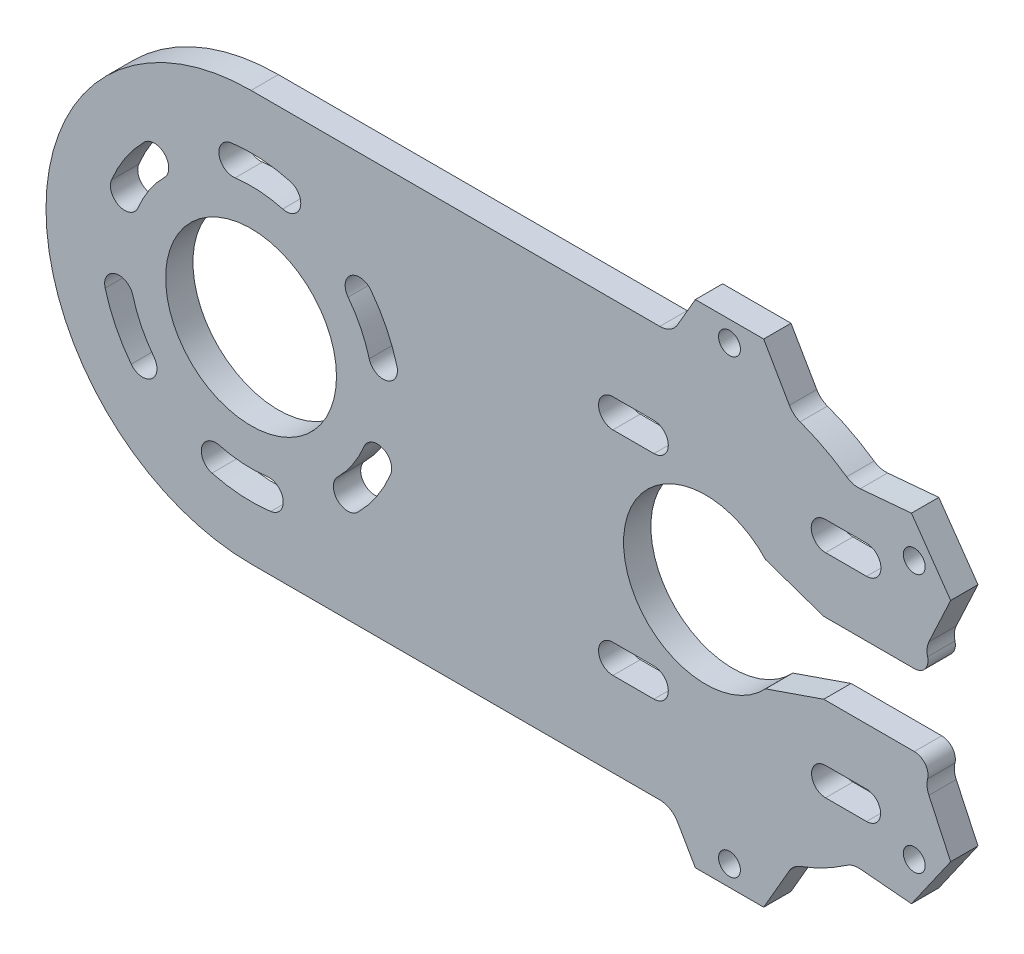
SolidWorks part; units mm, degrees
material "7075-T6 (SN)"
ref_plane "Ebene vorne" through (0, 0, 0) normal (0, 0, 1) x (1, 0, 0)
ref_plane "Ebene oben" through (0, 0, 0) normal (0, 1, 0) x (1, 0, 0)
ref_plane "Ebene rechts" through (0, 0, 0) normal (1, 0, 0) x (0, 0, -1)
sketch "Skizze1" plane through (0, 0, 0) normal (0, 0, 1) x (1, 0, 0)
  line L0 (60.6188, -25.1224) -> (53.122, -24.4665)
  line L1 (42.7599, -29.8607) -> (38.9972, -36.3779)
  line L2 (38.9972, -36.3779) -> (28.9972, -36.3779)
  line L3 (28.9972, -36.3779) -> (26.3991, -31.8779)
  line L4 (23.801, -30.3779) -> (-36.0028, -30.3779)
  line L5 (-36.0028, 29.6221) -> (23.801, 29.6221)
  line L6 (26.3991, 31.1221) -> (28.9972, 35.6221)
  line L7 (28.9972, 35.6221) -> (38.9972, 35.6221)
  line L8 (38.9972, 35.6221) -> (42.7599, 29.1049)
  line L9 (53.122, 23.7107) -> (60.6188, 24.3666)
  line L10 (60.6188, 24.3666) -> (66.3546, 16.1751)
  line L11 (66.3546, 16.1751) -> (63.1738, 9.3539)
  line L12 (61.0423, 4.8721) -> (47.7853, 4.8721)
  line L13 (47.7853, 4.8721) -> (39.265, 7.8151)
  line L14 (39.265, -8.5709) -> (47.7853, -5.6279)
  line L15 (47.7853, -5.6279) -> (61.0423, -5.6279)
  line L16 (63.1738, -10.1097) -> (66.3546, -16.9309)
  line L17 (66.3546, -16.9309) -> (60.6188, -25.1224)
  line L18 (54.0535, -13.8842) -> (48.0535, -13.8842)
  line L19 (48.0535, -17.9842) -> (54.0535, -17.9842)
  line L20 (22.9409, -13.8342) -> (16.9409, -13.8342)
  line L21 (16.9409, -18.0342) -> (22.9409, -18.0342)
  line L22 (54.0535, 17.2785) -> (48.0535, 17.2785)
  line L23 (48.0535, 13.0785) -> (54.0535, 13.0785)
  line L24 (22.9409, 17.2785) -> (16.9409, 17.2785)
  line L25 (16.9409, 13.0785) -> (22.9409, 13.0785)
  arc A0 (53.122, -24.4665) -> (51.1457, -24.9935) centre (52.8605, -27.4551) ccw
  arc A1 (44.3252, -28.544) -> (51.1457, -24.9935) centre (33.9972, -0.3779) ccw
  arc A2 (44.3252, -28.544) -> (42.7599, -29.8607) centre (45.358, -31.3607) ccw
  arc A3 (26.3991, -31.8779) -> (23.801, -30.3779) centre (23.801, -33.3779) ccw
  arc A4 (-36.0028, 29.6221) -> (-36.0028, -30.3779) centre (-36.0028, -0.3779) ccw
  arc A5 (23.801, 29.6221) -> (26.3991, 31.1221) centre (23.801, 32.6221) ccw
  arc A6 (42.7599, 29.1049) -> (44.3252, 27.7883) centre (45.358, 30.6049) ccw
  arc A7 (51.1457, 24.2378) -> (44.3252, 27.7883) centre (33.9972, -0.3779) ccw
  arc A8 (51.1457, 24.2378) -> (53.122, 23.7107) centre (52.8605, 26.6993) ccw
  arc A9 (63.1738, 9.3539) -> (62.9825, 7.3577) centre (65.8927, 8.086) ccw
  arc A10 (61.0423, 4.8721) -> (62.9825, 7.3577) centre (61.0423, 6.8721) ccw
  arc A11 (39.265, 7.8151) -> (39.265, -8.5709) centre (30.4972, -0.3779) ccw
  arc A12 (62.9825, -8.1135) -> (61.0423, -5.6279) centre (61.0423, -7.6279) ccw
  arc A13 (62.9825, -8.1135) -> (63.1738, -10.1097) centre (65.8927, -8.8418) ccw
  circle A14 centre (61.0292, -19.3059) radius 1.6
  circle A15 centre (33.9972, -33.3779) radius 1.6
  arc A16 (48.0535, -13.8842) -> (48.0535, -17.9842) centre (48.0535, -15.9342) ccw
  arc A17 (54.0535, -17.9842) -> (54.0535, -13.8842) centre (54.0535, -15.9342) ccw
  arc A18 (16.9409, -13.8342) -> (16.9409, -18.0342) centre (16.9409, -15.9342) ccw
  arc A19 (22.9409, -18.0342) -> (22.9409, -13.8342) centre (22.9409, -15.9342) ccw
  arc A20 (-40.6357, -17.668) -> (-33.6664, -18.1248) centre (-36.0028, -0.3779) ccw
  arc A21 (-40.6357, -17.668) -> (-41.7227, -21.7248) centre (-41.1792, -19.6964) ccw
  arc A22 (-41.7227, -21.7248) -> (-33.1182, -22.2888) centre (-36.0028, -0.3779) ccw
  arc A23 (-33.1182, -22.2888) -> (-33.6664, -18.1248) centre (-33.3923, -20.2068) ccw
  arc A24 (-20.3757, -16.0049) -> (-15.5851, -8.8352) centre (-36.0028, -0.3779) ccw
  arc A25 (-15.5851, -8.8352) -> (-19.4654, -7.2279) centre (-17.5252, -8.0316) ccw
  arc A26 (-23.3456, -13.0351) -> (-19.4654, -7.2279) centre (-36.0028, -0.3779) ccw
  arc A27 (-23.3456, -13.0351) -> (-20.3757, -16.0049) centre (-21.8607, -14.52) ccw
  arc A28 (-53.5359, -13.8315) -> (-50.2038, -11.2747) centre (-51.8699, -12.5531) ccw
  arc A29 (-53.2929, -5.0107) -> (-50.2038, -11.2747) centre (-36.0028, -0.3779) ccw
  arc A30 (-53.2929, -5.0107) -> (-57.3498, -6.0978) centre (-55.3213, -5.5543) ccw
  arc A31 (-57.3498, -6.0978) -> (-53.5359, -13.8315) centre (-36.0028, -0.3779) ccw
  circle A32 centre (-36.0028, -0.3779) radius 12.5
  circle A33 centre (61.0292, 18.5501) radius 1.6
  circle A34 centre (33.9972, 32.6221) radius 1.6
  arc A35 (-14.6558, 5.342) -> (-18.4697, 13.0757) centre (-36.0028, -0.3779) ccw
  arc A36 (-18.4697, 13.0757) -> (-21.8018, 10.5189) centre (-20.1357, 11.7973) ccw
  arc A37 (-18.7127, 4.255) -> (-21.8018, 10.5189) centre (-36.0028, -0.3779) ccw
  arc A38 (-18.7127, 4.255) -> (-14.6558, 5.342) centre (-16.6843, 4.7985) ccw
  arc A39 (48.0535, 17.2785) -> (48.0535, 13.0785) centre (48.0535, 15.1785) ccw
  arc A40 (54.0535, 13.0785) -> (54.0535, 17.2785) centre (54.0535, 15.1785) ccw
  arc A41 (16.9409, 17.2785) -> (16.9409, 13.0785) centre (16.9409, 15.1785) ccw
  arc A42 (22.9409, 13.0785) -> (22.9409, 17.2785) centre (22.9409, 15.1785) ccw
  arc A43 (-48.66, 12.2793) -> (-52.5402, 6.4721) centre (-36.0028, -0.3779) ccw
  arc A44 (-48.66, 12.2793) -> (-51.6299, 15.2492) centre (-50.1449, 13.7642) ccw
  arc A45 (-51.6299, 15.2492) -> (-56.4205, 8.0794) centre (-36.0028, -0.3779) ccw
  arc A46 (-56.4205, 8.0794) -> (-52.5402, 6.4721) centre (-54.4804, 7.2758) ccw
  arc A47 (-38.8874, 21.533) -> (-38.3392, 17.369) centre (-38.6133, 19.451) ccw
  arc A48 (-31.3699, 16.9122) -> (-38.3392, 17.369) centre (-36.0028, -0.3779) ccw
  arc A49 (-31.3699, 16.9122) -> (-30.2829, 20.9691) centre (-30.8264, 18.9406) ccw
  arc A50 (-30.2829, 20.9691) -> (-38.8874, 21.533) centre (-36.0028, -0.3779) ccw
extrude "Aufsatz-Linear austragen1" add sketch "Skizze1" along normal blind 4
